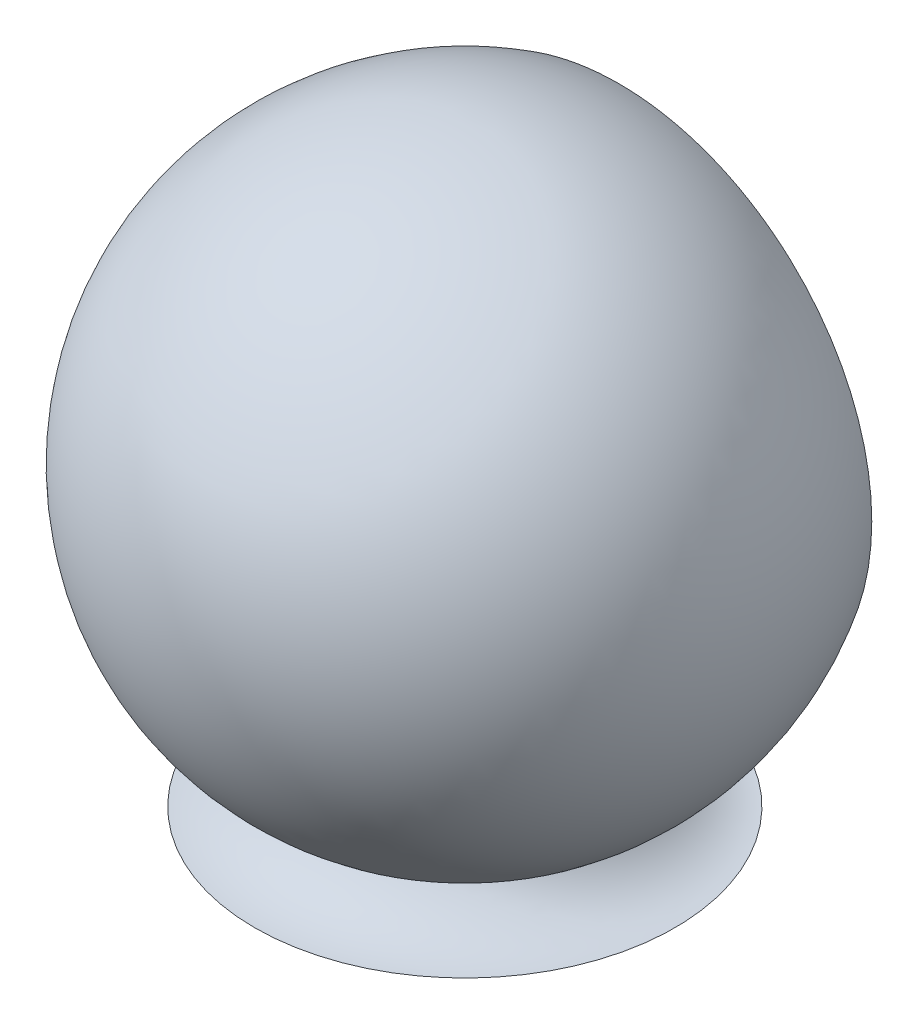
SolidWorks part; units mm, degrees
ref_plane "前视基准面" through (0, 0, 0) normal (0, 0, 1) x (1, 0, 0)
ref_plane "上视基准面" through (0, 0, 0) normal (0, 1, 0) x (1, 0, 0)
ref_plane "右视基准面" through (0, 0, 0) normal (1, 0, 0) x (0, 0, -1)
sketch "草图1" plane through (0, 0, 0) normal (0, 0, 1) x (1, 0, 0)
  line L0 (0, -102.0758) -> (0, 102.0758)
  arc A0 (0, -102.0758) -> (0, 102.0758) centre (0, 0) ccw
revolve "旋转1" add sketch "草图1" angle 360 about L0
sketch "草图2" plane through (0, 0, 0) normal (0, 0, 1) x (1, 0, 0)
  line L0 (0, -95.4991) -> (0, 95.4991)
  arc A0 (0, -95.4991) -> (0, 95.4991) centre (0, 0) ccw
revolve "切除-旋转1" cut sketch "草图2" angle 360 about L0 region at (40.5311, 0, 0)
sketch "草图3" plane through (0, 0, 0) normal (0, 0, 1) x (1, 0, 0)
  circle A0 centre (0, 0) radius 87.1214
extrude "切除-拉伸1" cut sketch "草图3" against normal blind 138
sketch "草图5" plane through (0, 0, 0) normal (0, 0, 1) x (1, 0, 0)
  circle A0 centre (0, 0) radius 79.8127
  circle A1 centre (0, 0) radius 74.8401
extrude "凸台-拉伸1" add sketch "草图5" along normal mid plane 99 separate body
sketch "草图7" plane through (0, 0, -49.5) normal (0, 0, -1) x (-1, 0, 0)
  line L0 (-62.0018, -37.1648) -> (62.0018, -37.1648)
  arc A0 (-62.0018, -37.1648) -> (62.0018, -37.1648) centre (0, 0) ccw
  arc A1 (-59.0074, -37.1648) -> (59.0074, -37.1648) centre (0, 0) ccw
extrude "凸台-拉伸3" add sketch "草图7" against normal blind 65 separate body contours A1 L0 A0 region at (60.5046, -38.4536, -49.5)
sketch "草图8" plane through (0, 0, 15.5) normal (0, 0, 1) x (1, 0, 0)
  line L0 (-59.0074, -37.1648) -> (59.0074, -37.1648)
  arc A0 (-59.0074, -37.1648) -> (59.0074, -37.1648) centre (0, 0) ccw
extrude "凸台-拉伸4" add sketch "草图8" against normal blind 2
sketch "草图9" plane through (0, 0, -49.5) normal (0, 0, -1) x (-1, 0, 0)
  line L0 (-62.0018, -37.1648) -> (62.0018, -37.1648)
  arc A0 (-62.0018, -37.1648) -> (62.0018, -37.1648) centre (0, 0) ccw
extrude "凸台-拉伸5" add sketch "草图9" along normal blind 3
sketch "草图10" plane through (0, 0, -52.5) normal (0, 0, -1) x (-1, 0, 0)
  line L1 (-19.3487, -43.6375) -> (19.3487, -43.6375)
  line L2 (-19.3487, -43.6375) -> (-19.3487, -51.4102)
  line L3 (-19.3487, -51.4102) -> (19.3487, -51.4102)
  line L4 (19.3487, -43.6375) -> (19.3487, -51.4102)
  line L5 (-19.3487, -43.6375) -> (19.3487, -51.4102) construction
  line L6 (-19.3487, -51.4102) -> (19.3487, -43.6375) construction
  point P0 (0, -47.5238)
extrude "切除-拉伸2" cut sketch "草图10" against normal blind 2
fillet "圆角1" radius 1 7 edges at (0, -51.4102, -52.5) (-19.3487, -47.5238, -50.5) (19.3487, -47.5238, -50.5) (0, -43.6375, -50.5) (-19.3487, -47.5238, -52.5) (19.3487, -47.5238, -52.5) (0, -43.6375, -52.5)
ref_plane "基准面1" through (0, 0, -18) normal (0, 0, 1) x (1, 0, 0)
sketch "草图12" plane through (0, 0, 0) normal (0, 1, 0) x (1, 0, 0)
  line L0 (-59.0074, 18) -> (59.0866, 18)
  line L1 (-59.0074, -13.5) -> (-59.0074, 49.5) construction
  line L2 (-52.1314, 18) -> (52.1314, 18) construction
  circle A0 centre (0.0396, 18) radius 1.5
extrude "凸台-拉伸6" add sketch "草图12" along normal blind 78 contours L0 A0 | L0 A0 region at (0.0396, 0, -18.6366) region at (0.0396, 0, -17.3634)
sketch "草图14" plane through (0, 0, 0) normal (1, 0, 0) x (0, 0, -1)
  line L0 (16.5, 0) -> (19.5, 0) construction
  circle A0 centre (18, 0) radius 1.5
extrude "凸台-拉伸7" add sketch "草图14" along normal mid plane 3
sketch "草图15" plane through (0, 0, -18) normal (0, 0, 1) x (1, 0, 0)
  line L0 (-67.0985, -24.551) -> (-67.8857, -24.839)
  line L1 (-71.449, 0) -> (-72.2872, 0)
  arc A0 (-72.2872, 0) -> (-67.8857, -24.839) centre (0, 0) ccw
  arc A1 (-71.449, 0) -> (-67.0985, -24.551) centre (0, 0) ccw
extrude "凸台-拉伸8" add sketch "草图15" along normal mid plane 63 separate body
sketch "草图16" plane through (0, 0, 0) normal (0, 1, 0) x (1, 0, 0)
  line L1 (-72.2872, 49.5) -> (-71.449, 49.5)
  line L2 (-72.2872, 49.5) -> (-72.2872, -13.5)
  line L3 (-72.2872, -13.5) -> (-71.449, -13.5)
  line L4 (-71.449, 49.5) -> (-71.449, -13.5)
extrude "凸台-拉伸9" add sketch "草图16" along normal blind 1
sketch "草图17" plane through (-71.449, 0, 0) normal (1, 0, 0) x (0, 0, -1)
  line L1 (-13.5, 1) -> (49.5, 1)
  line L2 (-13.5, 1) -> (-13.5, 0)
  line L3 (-13.5, 0) -> (49.5, 0)
  line L4 (49.5, 1) -> (49.5, 0)
extrude "凸台-拉伸10" add sketch "草图17" along normal blind 16
sketch "草图18" plane through (0, 1, 0) normal (0, 1, 0) x (1, 0, 0)
  line L0 (-67.1858, 44.3666) -> (-67.1858, 48.0487)
  line L1 (-70.4997, 48.0487) -> (-57.0601, 48.0487)
  line L2 (-70.4997, 48.0487) -> (-70.4997, -12.3374)
  line L3 (-70.4997, -12.3374) -> (-57.0601, -12.3374)
  line L4 (-57.0601, 48.0487) -> (-57.0601, -12.3374)
  line L5 (-68.8428, 46.0236) -> (-58.3488, 46.0236)
  line L6 (-68.8428, 46.0236) -> (-68.8428, -11.0487)
  line L7 (-68.8428, -11.0487) -> (-58.3488, -11.0487)
  line L8 (-58.3488, 46.0236) -> (-58.3488, -11.0487)
  line L9 (-67.1858, 44.3666) -> (-60.0058, 44.3666)
  line L10 (-67.1858, 44.3666) -> (-67.1858, -9.9441)
  line L11 (-67.1858, -9.9441) -> (-60.0058, -9.9441)
  line L12 (-60.0058, 44.3666) -> (-60.0058, -9.9441)
  line L13 (-65.713, 42.1574) -> (-61.4786, 42.1574)
  line L14 (-65.713, 42.1574) -> (-65.713, -8.2871)
  line L15 (-65.713, -8.2871) -> (-61.4786, -8.2871)
  line L16 (-61.4786, 42.1574) -> (-61.4786, -8.2871)
  line L17 (-68.8428, -11.0487) -> (-68.8428, -12.3374)
  line L18 (-68.8428, 46.0236) -> (-68.8428, 48.0487)
  line L19 (-58.3488, 46.0236) -> (-58.3488, 48.0487)
  line L20 (-58.3488, -11.0487) -> (-58.3488, -12.3374)
  line L21 (-67.1858, -9.9441) -> (-67.1858, -12.6312)
  line L22 (-60.0058, -9.9441) -> (-60.0058, -12.3374)
  line L23 (-65.713, -8.2871) -> (-65.713, -12.3374)
  line L24 (-61.4786, -8.2871) -> (-61.4786, -12.3374)
  line L25 (-64.4547, 40.606) -> (-62.7466, 40.606)
  line L26 (-64.4547, 40.606) -> (-64.4547, -6.726)
  line L27 (-64.4547, -6.726) -> (-62.7466, -6.726)
  line L28 (-62.7466, 40.606) -> (-62.7466, -6.726)
  line L29 (-60.0058, 44.3666) -> (-60.0058, 48.0487)
  line L30 (-65.713, 42.1574) -> (-65.713, 48.0487)
  line L31 (-61.4786, 42.1574) -> (-61.4786, 48.0487)
  line L32 (-64.4547, 40.606) -> (-64.4547, 48.0487)
  line L33 (-62.7466, 40.606) -> (-62.7466, 48.0487)
  line L34 (-64.4547, -6.726) -> (-64.4547, -12.3374)
  line L35 (-62.7466, -6.726) -> (-62.7466, -12.3374)
extrude "切除-拉伸4" cut sketch "草图18" against normal blind 3 contours L6 L18 L1 L2 L3 L17 | L8 L20 L3 L4 L1 L19 | L5 L30 L1 L0 | L14 L30 L9 L10 L11 L23 | L9 L30 L5 L0 | L23 L7 L21 L3 | L23 L11 L21 L7 | L11 L24 L7 L22 | L7 L24 L3 L22 | L31 L16 L24 L11 L12 L9 | L31 L9 L29 L5 | L31 L5 L29 L1 | L5 L33 L1 L32 | L9 L33 L5 L32 | L13 L33 L9 L32 | L25 L33 L13 L32 | L28 L25 L26 L27 | L35 L27 L34 L15 | L35 L15 L34 L11 | L35 L11 L34 L7 | L35 L7 L34 L3 region at (-66.4494, 1, -45.1951) region at (-66.4494, 1, -17.2113) region at (-66.4494, 1, -47.0361) region at (-66.4494, 1, 10.4964) region at (-69.6712, 1, -17.8556) region at (-63.6007, 1, -45.1951) region at (-63.6007, 1, -43.262) region at (-66.4494, 1, 11.6931) region at (-63.6007, 1, -47.0361) region at (-63.6007, 1, -41.3817) region at (-63.6007, 1, 9.1156) region at (-63.6007, 1, 10.4964) region at (-60.7422, 1, -45.1951) region at (-60.7422, 1, -17.2113) region at (-63.6007, 1, -16.94) region at (-63.6007, 1, 7.5066) region at (-63.6007, 1, 11.6931) region at (-60.7422, 1, -47.0361) region at (-60.7422, 1, 10.4964) region at (-60.7422, 1, 11.6931) region at (-57.7045, 1, -17.8556)
sketch "草图19" plane through (-55.449, 0, 0) normal (1, 0, 0) x (0, 0, -1)
  line L1 (-11.244, -0.8033) -> (47.0435, -0.8033)
  line L2 (-13.5, -2.5052) -> (-13.5, -4.3984)
  line L3 (-13.5, -24.551) -> (47.0435, -24.551)
  line L5 (-11.244, -2.5052) -> (47.0435, -2.5052)
  line L6 (-11.244, -12.6771) -> (47.0435, -12.6771)
  line L7 (-11.244, -4.3984) -> (47.0435, -4.3984)
  line L8 (-11.244, -6.6288) -> (47.0435, -6.6288)
  line L9 (-11.244, -8.3387) -> (47.0435, -8.3387)
  line L10 (-11.244, -10.0487) -> (47.0435, -10.0487)
  line L11 (-11.244, -15.3056) -> (47.0435, -15.3056)
  line L12 (-11.244, -17.0156) -> (47.0435, -17.0156)
  line L13 (-11.244, -18.7255) -> (47.0435, -18.7255)
  line L14 (-11.244, -20.9559) -> (47.0435, -20.9559)
  line L15 (-11.244, -22.8491) -> (47.0435, -22.8491)
  line L16 (-11.244, -24.551) -> (-11.244, -0.8033)
  line L17 (47.0435, -24.551) -> (47.0435, -0.8033)
extrude "切除-拉伸6" cut sketch "草图19" against normal blind 29 contours L15 L17 L14 L16 | L13 L17 L12 L16 | L11 L17 L6 L16 | L10 L17 L9 L16 | L8 L17 L7 L16 | L5 L17 L1 L16 region at (-55.449, -1.6543, -17.8997) region at (-55.449, -5.5136, -17.8997) region at (-55.449, -9.1937, -17.8997) region at (-55.449, -13.9914, -17.8997) region at (-55.449, -17.8706, -17.8997) region at (-55.449, -21.9025, -17.8997)
sketch "草图20" plane through (-1.5, 0, 0) normal (-1, 0, 0) x (0, 0, 1)
  circle A0 centre (-18, 0) radius 1.5
extrude "凸台-拉伸11" add sketch "草图20" along normal up to surface (53.949 mm away) up to face at (-55.449, 0.5, -18)
sketch "草图21" plane through (0, 0, -49.5) normal (0, 0, -1) x (-1, 0, 0)
  line L1 (-55.449, 0) -> (-72.2872, 0)
  line L3 (-49.5743, 24.839) -> (-67.8857, 24.839)
  arc A0 (-67.8857, 24.839) -> (-72.2872, 0) centre (0, 0) ccw
  arc A1 (-49.5743, 24.839) -> (-55.449, 0) centre (0, 0) ccw
extrude "凸台-拉伸12" add sketch "草图21" against normal blind 4 separate body
sketch "草图23" plane through (0, 0, -49.5) normal (0, 0, -1) x (-1, 0, 0)
  line L0 (-67.8857, 24.839) -> (-72.649, 24.839)
  line L1 (-72.2872, 0) -> (-76.778, 0)
  circle A0 centre (0, 0) radius 76.778
  circle A1 centre (0, 0) radius 74.8401
extrude "切除-拉伸7" cut sketch "草图23" against normal blind 65 contours A1 L0 A0 L1 region at (74.4086, 12.5362, -49.5)
sketch "草图24" plane through (0, 0, -49.5) normal (0, 0, -1) x (-1, 0, 0)
  line L0 (-74.8531, 12.3935) -> (-71.2169, 12.3935)
  line L1 (-71.3317, 11.7148) -> (-74.9623, 11.7148)
  line L2 (-74.8531, 12.3935) -> (-75.7711, 12.3935)
  line L3 (-74.9623, 11.7148) -> (-75.879, 11.7148)
  arc A0 (-71.2169, 12.3935) -> (-71.3317, 11.7148) centre (0, 0) ccw
  arc A1 (-67.8857, 24.839) -> (-72.2872, 0) centre (0, 0) ccw construction
  arc A2 (-75.7711, 12.3935) -> (-75.879, 11.7148) centre (0, 0) ccw
extrude "凸台-拉伸15" add sketch "草图24" against normal blind 4
sketch "草图26" plane through (0, 0, 15.5) normal (0, 0, 1) x (1, 0, 0)
  circle A0 centre (0, 0) radius 79.8127
ref_plane "基准面3" through (0, 0, 18.5) normal (0, 0, 1) x (1, 0, 0)
sketch "草图29" plane through (0, 0, 18.5) normal (0, 0, 1) x (1, 0, 0)
  circle A0 centre (0, 0) radius 79.8127
extrude "切除-拉伸11" cut sketch "草图29" along normal up to surface (31 mm away) up to face at (79.8127, 0, 49.5)
sketch "草图30" plane through (0, 0, 18.5) normal (0, 0, 1) x (1, 0, 0)
  line L0 (0, -79.8127) -> (79.8127, -79.8127)
  line L1 (50.3032, 0) -> (74.7494, 0)
  line L2 (50.3032, 0) -> (50.3032, -55.5787)
  line L4 (74.7494, 0) -> (74.7494, -5.6517)
  line L5 (50.3032, -77.785) -> (50.3032, -79.8127)
  line L6 (74.7494, -77.785) -> (74.7494, -79.8127)
  arc A0 (73.2388, 0) -> (50.3032, -53.2307) centre (0, 0) ccw
  arc A1 (50.3032, -55.5787) -> (74.7494, -5.6517) centre (0, 0) ccw
extrude "凸台-拉伸19" add sketch "草图30" along normal blind 27 contours L2 A1 L4 L1 region at (60.3085, -21.4061, 18.5)
sketch "草图32" plane through (0, 0, 45.5) normal (0, 0, 1) x (1, 0, 0)
  line L0 (50.3032, -55.5787) -> (50.3032, 0)
  line L1 (50.3032, 0) -> (74.9627, 0)
  arc A0 (50.3032, -55.5787) -> (74.9627, 0) centre (0, 0) ccw
extrude "凸台-拉伸21" add sketch "草图32" along normal blind 1
sketch "草图33" plane through (0, 0, 0) normal (0, 1, 0) x (1, 0, 0)
  line L1 (52.9591, -21.1817) -> (72.6546, -21.1817)
  line L2 (52.9591, -21.1817) -> (52.9591, -44.1599)
  line L3 (52.9591, -44.1599) -> (72.6546, -44.1599)
  line L4 (72.6546, -21.1817) -> (72.6546, -44.1599)
sketch "草图34" plane through (0, 0, 46.5) normal (0, 0, 1) x (1, 0, 0)
  line L0 (73.2774, -2.0796) -> (51.8945, -2.0796)
  line L1 (51.8945, -2.0796) -> (51.8945, -51.777)
  arc A1 (51.8945, -51.777) -> (73.2774, -2.0796) centre (0, 0) ccw
extrude "切除-拉伸13" cut sketch "草图34" against normal blind 25
extrude "切除-拉伸14" cut sketch "草图33" against normal blind 3
sketch "草图35" plane through (0, 0, 46.5) normal (0, 0, 1) x (1, 0, 0)
  line L0 (50.3032, -55.5787) -> (50.3032, 0)
  line L1 (50.3032, 0) -> (74.9365, 0)
  arc A0 (50.3032, -55.5433) -> (74.9365, 0) centre (0, 0) ccw
  arc M1 (73.2774, -2.0796) -> (51.8945, -51.777) centre (0, 0) cw
  line M2 (51.8945, -51.777) -> (51.8945, -2.0796)
  line M3 (51.8945, -2.0796) -> (73.2774, -2.0796)
  line M5 (74.9627, 0) -> (50.3032, 0)
  line M6 (50.3032, 0) -> (50.3032, -55.5787)
extrude "凸台-拉伸23" add sketch "草图35" along normal blind 1 contours A0 M6 M5 M3 M1 M2 | M1 M3 M2 region at (50.9108, -27.7717, 46.5) region at (60.4517, -21.0242, 46.5)
sketch "草图36" plane through (0, 0, 0) normal (0, 0, 1) x (1, 0, 0)
  line L0 (0, -102.0758) -> (-72.4402, -102.0758)
  line L1 (0, -102.0758) -> (0, -97.8236)
  line L2 (-48.1672, -89.9966) -> (0, -97.8236)
  line L4 (0, -102.0758) -> (-72.4402, -102.0758)
  circle A0 centre (0, 0) radius 102.0758 construction
  arc A1 (-72.4402, -102.0758) -> (-48.1672, -89.9966) centre (-72.4402, -71.6481) ccw
  arc A2 (-72.4402, -102.0758) -> (-48.1672, -89.9966) centre (-72.4402, -71.6481) ccw
  circle A3 centre (0, 0) radius 102.0758
revolve "旋转16" add sketch "草图36" angle 360 about L1 region at (-20.2067, -96.9288, 0) region at (-41.9082, -98.533, 0)
sketch "草图37" plane through (0, 0, 0) normal (0, 1, 0) x (1, 0, 0)
  circle A0 centre (0.0396, 18) radius 2
extrude "切除-拉伸15" cut sketch "草图37" along normal blind 74
sketch "草图38" plane through (1.5, 0, 0) normal (1, 0, 0) x (0, 0, -1)
  line L0 (19.5, 0) -> (16.5, 0) construction
  circle A0 centre (18, 0) radius 1.5
extrude "切除-拉伸16" cut sketch "草图38" against normal up to surface (56.949 mm away) up to face at (-55.449, 0.5088, -1.5724)
sketch "草图39" plane through (0, 0, 18.5) normal (0, 0, 1) x (1, 0, 0)
  line L0 (-67.8857, -24.839) -> (-67.8668, -24.839)
  line L1 (0, 0) -> (-72.3851, -0.6525)
  line L2 (-72.3851, -0.6525) -> (72.3851, 0.6525)
  arc A0 (-72.3851, -0.6525) -> (72.3851, 0.6525) centre (0, 0) ccw
  circle A1 centre (0, 0) radius 2.4698
extrude "凸台-拉伸25" add sketch "草图39" against normal blind 1 contours A1 L2 A0 region at (0.2772, -30.7558, 18.5)
sketch "草图40" plane through (0, 0, 18.5) normal (0, 0, 1) x (1, 0, 0)
  circle A0 centre (0, 0) radius 3.5
extrude "凸台-拉伸26" add sketch "草图40" against normal blind 3
sketch "草图42" plane through (-55.449, 0, 0) normal (1, 0, 0) x (0, 0, -1)
  circle A0 centre (-12.9528, 0.4636) radius 0.5362
extrude "凸台-拉伸27" add sketch "草图42" along normal blind 55
sketch "草图43" plane through (0, 0, 15.5) normal (0, 0, -1) x (-1, 0, 0)
  circle A0 centre (0, 0) radius 1.4667
extrude "凸台-拉伸28" add sketch "草图43" along normal blind 4
equation "\"s\"=360"
